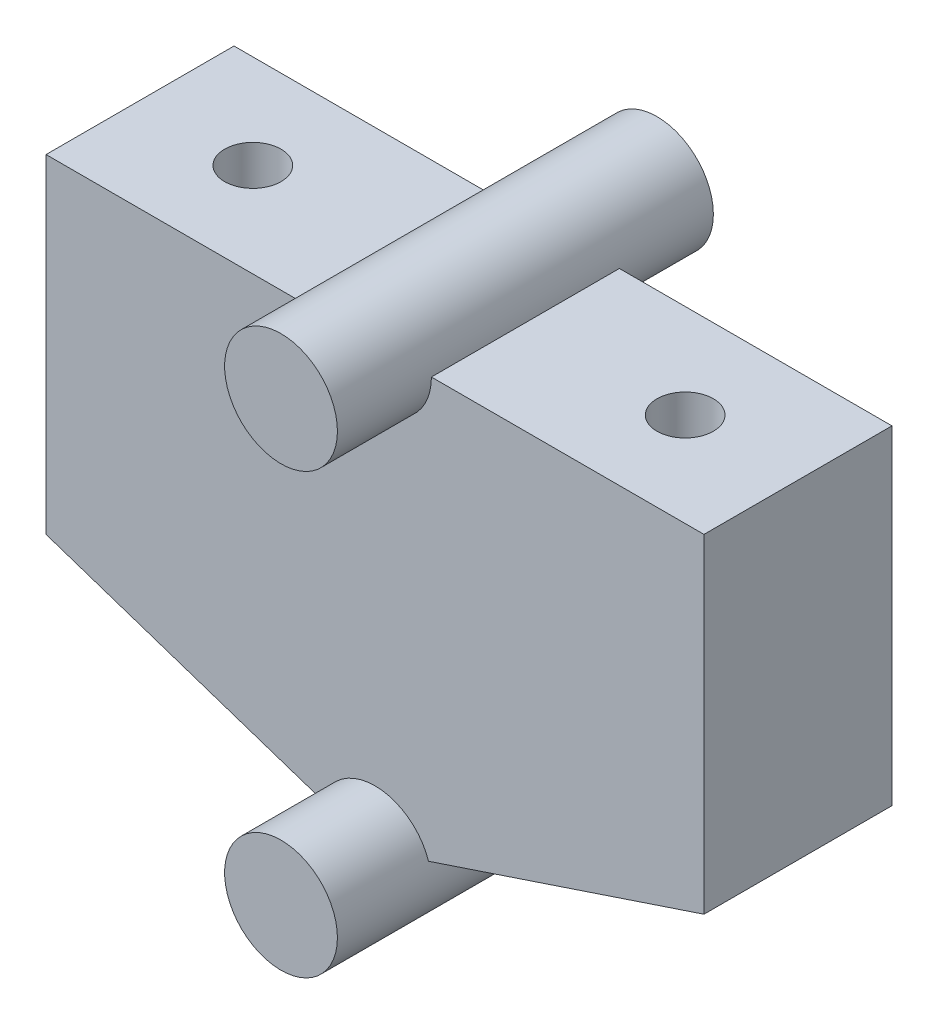
SolidWorks part; units mm, degrees
ref_plane "Front Plane" through (0, 0, 0) normal (0, 0, 1) x (1, 0, 0)
ref_plane "Top Plane" through (0, 0, 0) normal (0, 1, 0) x (1, 0, 0)
ref_plane "Right Plane" through (0, 0, 0) normal (1, 0, 0) x (0, 0, -1)
sketch "Sketch1" plane through (0, 0, 0) normal (0, 0, 1) x (1, 0, 0)
  line L0 (-17.5, -8.75) -> (-2.846, -13.6347)
  line L1 (-17.5, 8.75) -> (17.5, 8.75)
  line L2 (-17.5, 8.75) -> (-17.5, -8.75)
  line L3 (17.5, 8.75) -> (17.5, -8.75)
  line L4 (-17.5, 8.75) -> (17.5, -8.75) construction
  line L5 (-17.5, -8.75) -> (17.5, 8.75) construction
  line L6 (2.846, -13.6347) -> (17.5, -8.75)
  line L7 (-17.5, -8.75) -> (0, -14.5833) construction
  circle A0 centre (0, -14.5833) radius 3
  point P0 (0, 0)
  dimension "D4" = 6
  dimension "D1" = 17.5
  dimension "D2" = 35
  dimension "D3" = 23.3333
extrude "Boss-Extrude1" add sketch "Sketch1" along normal blind 10 contours A0 L6 L3 L1 L2 L0 region at (0, -1.3434, 0)
extrude "Boss-Extrude2" add sketch "Sketch1<3>" along normal blind 15 and the other way blind 5 contours A0 region at (0, -14.5833, 0)
sketch "Sketch1<3>" plane through (0, 0, 0) normal (0, 0, 1) x (1, 0, 0) same geometry as "Sketch1"
sketch "Sketch2" plane through (0, 8.75, 0) normal (0, 1, 0) x (1, 0, 0)
  line L0 (-17.5, 0) -> (17.5, 0) construction
  line L1 (-17.5, -10) -> (-17.5, 0) construction
  line L2 (0, -55) -> (0, 55) construction
  circle A0 centre (-11.5, -5) radius 1.5
  circle A1 centre (11.5, -5) radius 1.5
  dimension "D1" = 3
  dimension "D2" = 5
  dimension "D3" = 6
extrude "Cut-Extrude1" cut sketch "Sketch2" against normal through all
sketch "Sketch3" plane through (0, 0, 10) normal (0, 0, 1) x (1, 0, 0)
  line L0 (-17.5, 8.75) -> (17.5, 8.75) construction
  circle A0 centre (0, 8.75) radius 3
  dimension "D1" = 6
extrude "Boss-Extrude3" add sketch "Sketch3" along normal blind 5 and the other way blind 15
